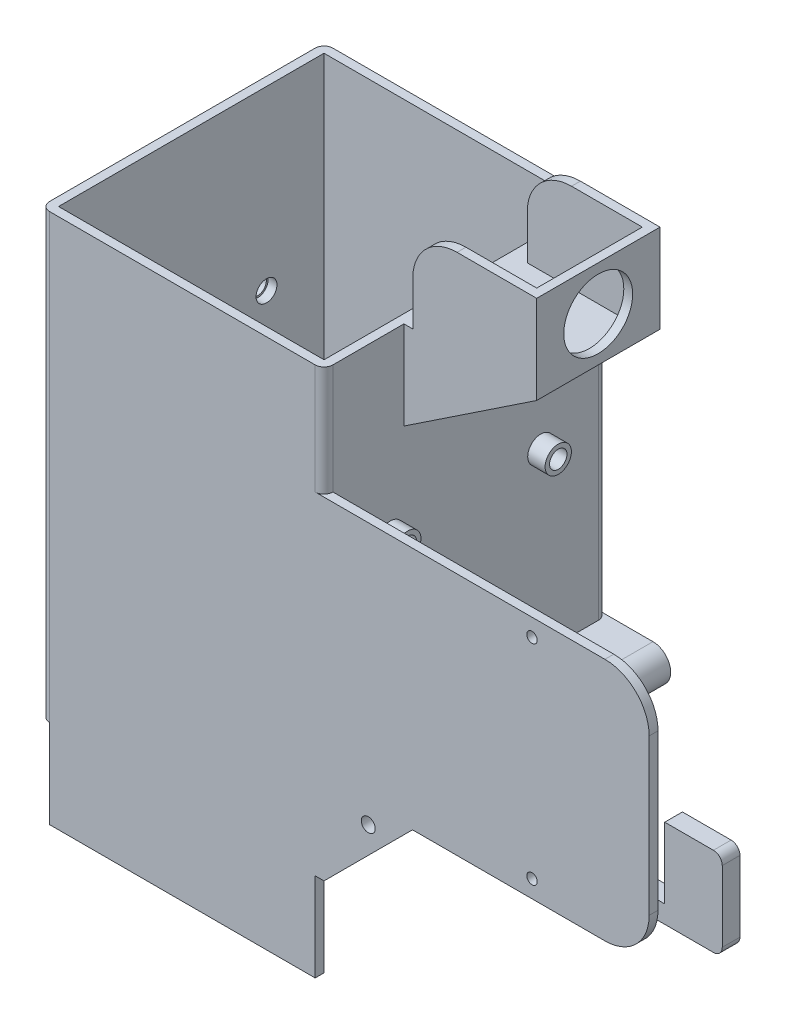
SolidWorks part; units mm, degrees
ref_plane "Front Plane" through (0, 0, 0) normal (0, 0, 1) x (1, 0, 0)
ref_plane "Top Plane" through (0, 0, 0) normal (0, 1, 0) x (1, 0, 0)
ref_plane "Right Plane" through (0, 0, 0) normal (1, 0, 0) x (0, 0, -1)
sketch "Sketch1" plane through (0, 0, 0) normal (0, 1, 0) x (1, 0, 0)
  line L1 (0, 0) -> (81.28, 0)
  line L2 (0, 0) -> (0, 81.28)
  line L3 (0, 81.28) -> (81.28, 81.28)
  line L4 (81.28, 0) -> (81.28, 81.28)
  line L5 (2.54, 2.54) -> (78.74, 2.54)
  line L6 (2.54, 2.54) -> (2.54, 78.74)
  line L7 (2.54, 78.74) -> (78.74, 78.74)
  line L8 (78.74, 2.54) -> (78.74, 78.74)
  dimension "D1" = 2.54
  dimension "D2" = 2.54
  dimension "D3" = 2.54
  dimension "D4" = 2.54
  dimension "D5" = 76.2
  dimension "D6" = 76.2
extrude "Boss-Extrude1" add sketch "Sketch1" along normal blind 177.8
sketch "Sketch2" plane through (0, 0, 0) normal (1, 0, 0) x (0, 0, -1)
  line L0 (109.0297, 38.1) -> (-23.7268, 38.1) construction
  line L1 (81.28, 0) -> (0, 0) construction
  line L2 (40.64, -8.2418) -> (40.64, 63.9342) construction
  line L3 (81.28, 177.8) -> (81.28, 0) construction
  line L5 (66.04, 0) -> (63.5, 0)
  line L6 (66.04, 0) -> (66.04, 38.1)
  line L7 (66.04, 38.1) -> (63.5, 38.1)
  line L8 (63.5, 0) -> (63.5, 38.1)
  dimension "D1" = 38.1
  dimension "D2" = 40.64
  dimension "D3" = 2.54
  dimension "D4" = 15.24
extrude "Boss-Extrude2" add sketch "Sketch2" against normal blind 25.4
sketch "Sketch3" plane through (0, 0, 0) normal (0, 0, 1) x (1, 0, 0)
  line L1 (81.28, 0) -> (78.74, 0)
  line L2 (81.28, 0) -> (81.28, 25.4)
  line L3 (81.28, 25.4) -> (78.74, 25.4)
  line L4 (78.74, 0) -> (78.74, 25.4)
  dimension "D1" = 2.54
  dimension "D2" = 25.4
extrude "Cut-Extrude1" cut sketch "Sketch3" against normal through all
sketch "Sketch7" plane through (0, 0, 0) normal (0, 0, 1) x (1, 0, 0)
  line L0 (81.28, 25.4) -> (106.68, 50.8)
  line L1 (106.68, 50.8) -> (81.28, 50.8)
  line L2 (81.28, 177.8) -> (81.28, 25.4) construction
  line L3 (81.28, 50.8) -> (81.28, 25.4)
  dimension "D1" = 45
  dimension "D2" = 25.4
extrude "Boss-Extrude3" add sketch "Sketch7" against normal blind 12.7
sketch "Sketch10" plane through (0, 0, -81.28) normal (0, 0, -1) x (-1, 0, 0)
  line L0 (-81.28, 25.4) -> (-81.28, 50.8)
  line L1 (-81.28, 177.8) -> (-81.28, 25.4) construction
  line L2 (-81.28, 50.8) -> (-106.68, 50.8)
  line L3 (-106.68, 50.8) -> (-81.28, 25.4)
  dimension "D1" = 45
  dimension "D2" = 25.4
extrude "Boss-Extrude4" add sketch "Sketch10" against normal blind 12.7
sketch "Sketch14" plane through (81.28, 0, 0) normal (1, 0, 0) x (0, 0, -1)
  line L0 (38.1, 50.8) -> (38.1, 25.4)
  line L1 (68.58, 25.4) -> (12.7, 25.4) construction
  line L2 (38.1, 25.4) -> (43.18, 25.4)
  line L3 (43.18, 25.4) -> (43.18, 50.8)
  line L4 (43.18, 50.8) -> (38.1, 50.8)
  line L5 (68.58, 50.8) -> (68.58, 25.4) construction
  dimension "D1" = 5.08
  dimension "D2" = 25.4
  dimension "D3" = 25.4
extrude "Boss-Extrude6" add sketch "Sketch14" along normal blind 76.2
sketch "Sketch16" plane through (0, 0, -38.1) normal (0, 0, 1) x (1, 0, 0)
  line L0 (157.48, 50.8) -> (81.28, 50.8) construction
  line L1 (140.97, 50.8) -> (117.84, 50.8)
  line L2 (140.97, 50.8) -> (140.97, 30.48)
  line L3 (140.97, 30.48) -> (117.84, 30.48)
  line L4 (117.84, 50.8) -> (117.84, 30.48)
  line L5 (157.48, 50.8) -> (157.48, 25.4) construction
  line L6 (157.48, 25.4) -> (81.28, 25.4) construction
  dimension "D1" = 16.51
  dimension "D2" = 23.13
  dimension "D3" = 5.08
extrude "Cut-Extrude2" cut sketch "Sketch16" against normal up to next
sketch "Sketch22" plane through (0, 0, 0) normal (0, 0, 1) x (1, 0, 0)
  line L0 (93.98, 45.72) -> (101.6, 45.72) construction
  line L1 (106.68, 50.8) -> (81.28, 50.8) construction
  line L2 (93.98, 50.8) -> (93.98, 45.72) construction
  line L4 (81.28, 25.4) -> (106.68, 50.8) construction
  circle A0 centre (93.98, 45.72) radius 2
  dimension "D3" = 4
  dimension "D1" = 5.08
  dimension "D2" = 12.7
extrude "Cut-Extrude6" cut sketch "Sketch22" against normal through all
sketch "Sketch28" plane through (81.28, 0, 0) normal (1, 0, 0) x (0, 0, -1)
  line L0 (40.64, 175.678) -> (40.64, 120.0937) construction
  line L1 (40.64, 184.0271) -> (40.64, -14.0592) construction
  line L2 (0, 177.8) -> (81.28, 177.8) construction
  line L3 (0, 177.8) -> (0, 50.8) construction
  line L5 (58.34, 177.8) -> (22.94, 177.8)
  line L6 (58.34, 177.8) -> (58.34, 127)
  line L7 (58.34, 127) -> (22.94, 127)
  line L8 (22.94, 177.8) -> (22.94, 127)
  line L9 (58.34, 177.8) -> (22.94, 127) construction
  line L10 (58.34, 127) -> (22.94, 177.8) construction
  point P8 (40.64, 109.22)
  dimension "D2" = 40.64
  dimension "D3" = 50.8
  dimension "D4" = 35.4
extrude "Boss-Extrude7" add sketch "Sketch28" along normal blind 38.1
sketch "Sketch30" plane through (0, 0, -22.94) normal (0, 0, 1) x (1, 0, 0)
  line L0 (81.28, 127) -> (119.38, 127)
  line L1 (119.38, 127) -> (119.38, 152.4)
  line L3 (119.38, 152.4) -> (81.28, 127)
  dimension "D1" = 25.4
  dimension "D2" = 33.69
extrude "Cut-Extrude8" cut sketch "Sketch30" against normal up to next
sketch "Sketch32" plane through (0, 177.8, 0) normal (0, 1, 0) x (1, 0, 0)
  line L0 (119.38, 58.34) -> (81.28, 58.34) construction
  line L1 (83.82, 55.8) -> (116.84, 55.8)
  line L2 (83.82, 55.8) -> (83.82, 25.48)
  line L3 (83.82, 25.48) -> (116.84, 25.48)
  line L4 (116.84, 55.8) -> (116.84, 25.48)
  line L5 (83.82, 55.8) -> (116.84, 25.48) construction
  line L6 (83.82, 25.48) -> (116.84, 55.8) construction
  line L7 (119.38, 58.34) -> (119.38, 22.94) construction
  line L8 (119.38, 22.94) -> (81.28, 22.94) construction
  line L9 (81.28, 58.34) -> (81.28, 81.28) construction
  point P0 (100.33, 40.64)
  dimension "D1" = 2.54
  dimension "D2" = 2.54
  dimension "D3" = 2.54
  dimension "D4" = 2.54
extrude "Cut-Extrude9" cut sketch "Sketch32" against normal blind 25.4
sketch "Sketch34" plane through (119.38, 0, 0) normal (1, 0, 0) x (0, 0, -1)
  line L0 (40.593, 147.7754) -> (40.593, 78.4323) construction
  line L1 (11.6001, 165.1) -> (93.4551, 165.1) construction
  line L2 (22.94, 177.8) -> (22.94, 152.4) construction
  line L3 (58.34, 177.8) -> (22.94, 177.8) construction
  circle A0 centre (40.593, 165.1) radius 9.89
  dimension "D3" = 19.78
  dimension "D1" = 17.653
  dimension "D2" = 12.7
extrude "Cut-Extrude13" cut sketch "Sketch34" against normal up to surface (40.64 mm away) up to face at (78.74, 101.6, -40.64)
sketch "Sketch37" plane through (0, 0, -63.5) normal (0, 0, 1) x (1, 0, 0)
  line L0 (-25.4, 38.1) -> (0, 38.1)
  line L1 (0, 38.1) -> (0, 52.7647)
  line L2 (0, 52.7647) -> (-25.4, 38.1)
  dimension "D1" = 30
extrude "Boss-Extrude9" add sketch "Sketch37" against normal up to surface (2.54 mm away) up to face at (-12.7, 19.05, -66.04)
sketch "Sketch38" plane through (0, 0, 0) normal (0, 0, 1) x (1, 0, 0)
  line L1 (0, 0) -> (2.54, 0)
  line L2 (0, 0) -> (0, 25.4)
  line L3 (0, 25.4) -> (2.54, 25.4)
  line L4 (2.54, 0) -> (2.54, 25.4)
  dimension "D1" = 25.4
  dimension "D2" = 2.54
extrude "Cut-Extrude15" cut sketch "Sketch38" against normal up to surface (63.5 mm away) up to face at (-12.7, 22.7162, -63.5)
sketch "Sketch40" plane through (81.28, 0, 0) normal (1, 0, 0) x (0, 0, -1)
  line L0 (-23.3344, 101.6) -> (103.8421, 101.6) construction
  line L1 (38.1, 25.4) -> (12.7, 25.4) construction
  line L2 (19.05, 177.8) -> (19.05, 25.4) construction
  line L3 (62.23, 177.8) -> (62.23, 25.4) construction
  line L6 (0, 177.8) -> (0, 50.8) construction
  line L7 (81.28, 177.8) -> (81.28, 50.8) construction
  line L8 (0, 177.8) -> (22.94, 177.8) construction
  line L9 (58.34, 177.8) -> (81.28, 177.8) construction
  line L10 (68.58, 25.4) -> (43.18, 25.4) construction
  circle A0 centre (19.05, 101.6) radius 3
  circle A1 centre (62.23, 101.6) radius 3
  dimension "D4" = 6
  dimension "D5" = 6
  dimension "D1" = 76.2
  dimension "D2" = 19.05
  dimension "D3" = 19.05
extrude "Cut-Extrude17" cut sketch "Sketch40" against normal up to surface (81.28 mm away) up to face at (0, 63.9912, -52.705)
sketch "Sketch41" plane through (81.28, 0, 0) normal (1, 0, 0) x (0, 0, -1)
  circle A0 centre (19.05, 101.6) radius 3.77
  circle A1 centre (19.05, 101.6) radius 2.5
  circle A2 centre (62.23, 101.6) radius 3.77
  circle A4 centre (62.23, 101.6) radius 2.5
  dimension "D1" = 1.27
  dimension "D2" = 1.27
extrude "Boss-Extrude10" add sketch "Sketch41" along normal blind 5
sketch "Sketch42" plane through (0, 0, 0) normal (-1, 0, 0) x (0, 0, 1)
  circle A0 centre (-62.23, 101.6) radius 2.5
  circle A1 centre (-62.23, 101.6) radius 3.77
  circle A2 centre (-19.05, 101.6) radius 2.5
  circle A3 centre (-19.05, 101.6) radius 3.77
  dimension "D1" = 1.27
  dimension "D2" = 1.27
extrude "Boss-Extrude11" add sketch "Sketch42" along normal blind 5
sketch "Sketch43" plane through (0, 177.8, 0) normal (0, 1, 0) x (1, 0, 0)
  line L1 (83.82, 58.34) -> (83.82, 22.94)
  line L3 (78.74, 2.54) -> (2.54, 2.54)
  line L4 (2.54, 2.54) -> (78.74, 2.54) construction
  line L5 (2.54, 2.54) -> (2.54, 78.74)
  line L6 (2.54, 78.74) -> (78.74, 78.74)
  line L11 (81.28, 81.28) -> (0, 81.28)
  line L12 (0, 81.28) -> (0, 0)
  line L13 (0, 0) -> (81.28, 0)
  line L19 (81.28, 81.28) -> (81.28, 58.34)
  line L21 (81.28, 58.34) -> (83.82, 58.34)
  line L22 (81.28, 0) -> (81.28, 22.94)
  line L23 (81.28, 22.94) -> (83.82, 22.94)
  line L24 (78.74, 78.74) -> (78.74, 2.54)
  line L25 (83.82, 55.8) -> (83.82, 25.48) construction
  line L26 (119.38, 22.94) -> (81.28, 22.94) construction
  line L27 (81.28, 81.28) -> (0, 81.28) construction
extrude "Cut-Extrude20" cut sketch "Sketch43" against normal blind 25.4
sketch "Sketch44" plane through (0, 0, 0) normal (0, 0, 1) x (1, 0, 0)
  line L0 (0, 152.4) -> (0, 25.4) construction
  line L1 (0, 50.8) -> (174.6, 50.8)
  line L2 (0, 50.8) -> (0, 120.8)
  line L3 (0, 120.8) -> (174.6, 120.8)
  line L4 (174.6, 50.8) -> (174.6, 120.8)
  line L5 (106.68, 50.8) -> (81.28, 50.8) construction
  line L6 (-25.4, 38.1) -> (-25.4, 0) construction
  line L7 (140.97, 50.8) -> (140.97, 120.8) construction
  line L8 (140.97, 30.48) -> (140.97, 50.8) construction
  circle A0 centre (140.97, 115.8) radius 1.5
  circle A1 centre (140.97, 55.8) radius 1.5
  dimension "D3" = 3
  dimension "D1" = 200
  dimension "D2" = 70
  dimension "D4" = 60
  dimension "D5" = 5
extrude "Boss-Extrude12" add sketch "Sketch44" against normal blind 2.54
fillet "Fillet1" radius 5.08 2 edges at (106.68, 50.8, -7.62) (106.68, 50.8, -74.93)
fillet "Fillet2" radius 12.7 2 edges at (174.6, 120.8, -1.27) (174.6, 50.8, -1.27)
fillet "Fillet3" radius 2.54 2 edges at (157.48, 50.8, -40.64) (157.48, 25.4, -40.64)
fillet "Fillet7" radius 12.7 1 edges at (-25.4, 38.1, -64.77)
fillet "Fillet9" radius 12.7 2 edges at (83.82, 177.8, -24.21) (83.82, 177.8, -57.07)
sketch "Sketch53" plane through (0, 0, 0) normal (0, -1, 0) x (-1, 0, 0)
  line L0 (-35.6591, 81.28) -> (-35.6591, 78.74)
  line L1 (-78.74, 81.28) -> (0, 81.28) construction
  line L2 (-78.74, 78.74) -> (-2.54, 78.74) construction
  line L3 (-35.6591, 78.74) -> (-45.72, 78.74)
  line L4 (-45.72, 78.74) -> (-45.72, 111.76)
  line L5 (-45.72, 111.76) -> (-15.24, 111.76)
  line L6 (-15.24, 111.76) -> (-15.24, 106.68)
  line L7 (-15.24, 106.68) -> (-40.64, 106.68)
  line L8 (-40.64, 106.68) -> (-40.64, 81.28)
  line L9 (-40.64, 81.28) -> (-35.6591, 81.28)
  line L12 (-81.28, 81.28) -> (-81.28, 96.103) construction
  line L13 (0, 81.28) -> (0, 96.103) construction
  dimension "D1" = 25.4
  dimension "D2" = 5.08
  dimension "D3" = 5.08
  dimension "D4" = 25.4
  dimension "D5" = 40.64
extrude "Boss-Extrude20" add sketch "Sketch53" against normal blind 88.9
sketch "Sketch54" plane through (0, 0, -111.76) normal (0, 0, -1) x (-1, 0, 0)
  line L0 (-30.48, 0) -> (-30.48, 88.9) construction
  line L1 (-15.24, 0) -> (-45.72, 0) construction
  line L2 (-15.24, 88.9) -> (-45.72, 88.9) construction
  circle A0 centre (-30.48, 76.2) radius 2.5
  circle A1 centre (-30.48, 44.45) radius 2.5
  circle A2 centre (-30.48, 12.7) radius 2.5
  dimension "D1" = 5
  dimension "D2" = 5
  dimension "D3" = 5
  dimension "D4" = 12.7
  dimension "D5" = 12.7
  dimension "D6" = 44.45
extrude "Cut-Extrude21" cut sketch "Sketch54" against normal up to next
sketch "Sketch55" plane through (0, 0, 0) normal (0, -1, 0) x (-1, 0, 0)
  line L0 (-78.74, 78.74) -> (-2.54, 78.74) construction
  line L1 (-15.24, 111.76) -> (-45.72, 111.76)
  line L2 (-15.24, 111.76) -> (-15.24, 78.74)
  line L3 (-15.24, 78.74) -> (-45.72, 78.74)
  line L4 (-45.72, 111.76) -> (-45.72, 78.74)
  line L5 (-45.72, 111.76) -> (-45.72, 81.28) construction
extrude "Boss-Extrude21" add sketch "Sketch55" against normal blind 2.54
fillet "Fillet12" radius 2.54 4 edges at (81.28, 136.6, 0) (81.28, 101.6, -81.28) (0, 76.2, -81.28) (0, 88.9, 0)
fillet "Fillet13" radius 2.54 2 edges at (15.24, 45.72, -106.68) (15.24, 44.45, -111.76)
